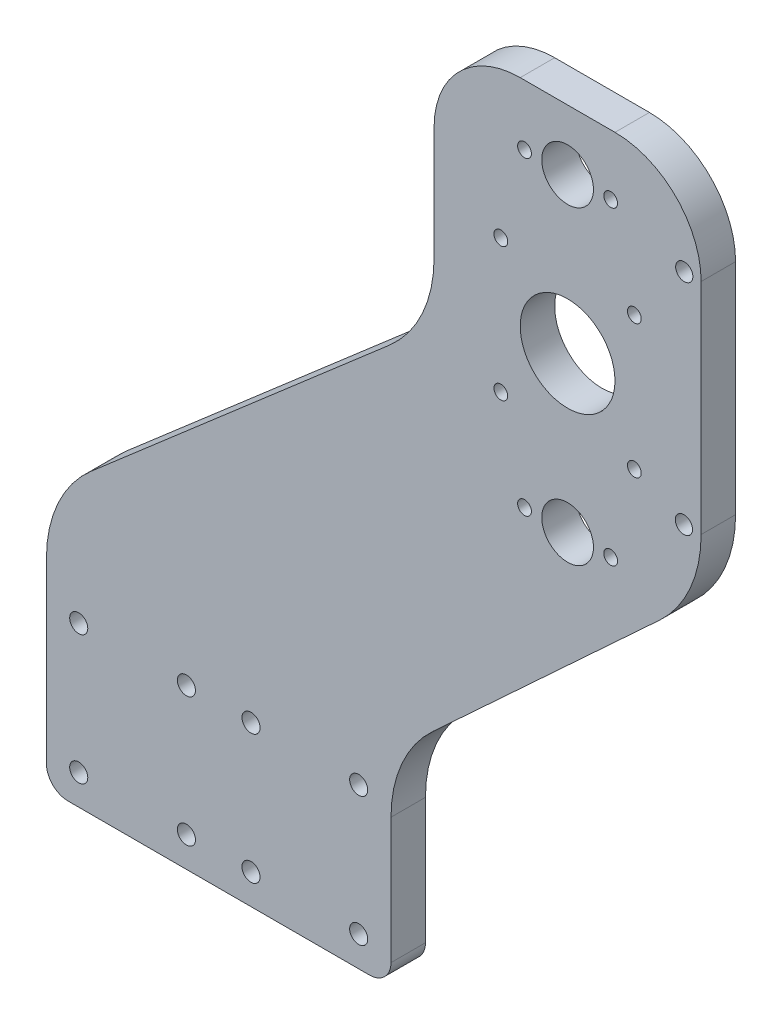
SolidWorks part; units mm, degrees
ref_plane "Front Plane" through (0, 0, 0) normal (0, 0, 1) x (1, 0, 0)
ref_plane "Top Plane" through (0, 0, 0) normal (0, 1, 0) x (1, 0, 0)
ref_plane "Right Plane" through (0, 0, 0) normal (1, 0, 0) x (0, 0, -1)
sketch "Sketch1" plane through (0, 0, 0) normal (0, 0, 1) x (1, 0, 0)
  line L0 (-23.731, -89.4451) -> (-23.731, -15.4242) construction
  line L1 (-58.731, -89.4451) -> (11.269, -89.4451)
  line L2 (-63.731, -84.4451) -> (-63.731, -43.1503)
  line L3 (-63.731, -84.4451) -> (-23.731, -84.4451) construction
  line L4 (16.269, -84.4451) -> (16.269, -55.2061)
  line L5 (46.269, 108.4996) -> (68.269, 108.4996)
  line L6 (26.269, 88.4996) -> (26.269, 62.2048)
  line L7 (57.269, 108.4996) -> (57.269, 22.5596) construction
  line L8 (88.269, 88.4996) -> (88.269, 37.6266)
  line L9 (-43.731, -67.4451) -> (-43.731, -84.4451) construction
  line L10 (-56.231, -52.4451) -> (-31.231, -52.4451) construction
  line L11 (15.9089, 39.5272) -> (-53.371, -20.4728)
  line L12 (78.6402, 15.6036) -> (25.8977, -33.1831)
  line L13 (-56.231, -52.4451) -> (-56.231, -82.4451) construction
  line L14 (-56.231, -82.4451) -> (-31.231, -82.4451) construction
  line L15 (-31.231, -52.4451) -> (-31.231, -82.4451) construction
  line L16 (-56.231, -52.4451) -> (-31.231, -82.4451) construction
  line L17 (-56.231, -82.4451) -> (-31.231, -52.4451) construction
  line L18 (57.269, 94.4996) -> (57.269, 22.5596) construction
  line L20 (41.769, 43.0296) -> (72.769, 43.0296) construction
  line L21 (41.769, 43.0296) -> (41.769, 74.0296) construction
  line L22 (41.769, 74.0296) -> (72.769, 74.0296) construction
  line L23 (72.769, 43.0296) -> (72.769, 74.0296) construction
  line L24 (41.769, 43.0296) -> (72.769, 74.0296) construction
  line L25 (41.769, 74.0296) -> (72.769, 43.0296) construction
  arc A0 (78.6402, 15.6036) -> (88.269, 37.6266) centre (58.269, 37.6266) ccw
  arc A1 (15.9089, 39.5272) -> (26.269, 62.2048) centre (-3.731, 62.2048) ccw
  arc A2 (16.269, -55.2061) -> (25.8977, -33.1831) centre (46.269, -55.2061) cw
  arc A3 (-63.731, -43.1503) -> (-53.371, -20.4728) centre (-33.731, -43.1503) cw
  arc A4 (88.269, 88.4996) -> (68.269, 108.4996) centre (68.269, 88.4996) ccw
  arc A5 (46.269, 108.4996) -> (26.269, 88.4996) centre (46.269, 88.4996) ccw
  arc A6 (16.269, -84.4451) -> (11.269, -89.4451) centre (11.269, -84.4451) cw
  arc A7 (-58.731, -89.4451) -> (-63.731, -84.4451) centre (-58.731, -84.4451) cw
  circle A8 centre (-56.231, -52.4451) radius 2.1
  circle A9 centre (-31.231, -52.4451) radius 2.1
  circle A10 centre (-31.231, -82.4451) radius 2.1
  circle A11 centre (-56.231, -82.4451) radius 2.1
  circle A12 centre (8.769, -82.4451) radius 2.1
  circle A13 centre (-16.231, -82.4451) radius 2.1
  circle A14 centre (-16.231, -52.4451) radius 2.1
  circle A15 centre (8.769, -52.4451) radius 2.1
  circle A16 centre (57.269, 94.4996) radius 6
  circle A17 centre (57.269, 22.5596) radius 6
  circle A18 centre (57.269, 58.5296) radius 11
  circle A19 centre (41.769, 74.0296) radius 1.6
  circle A20 centre (72.769, 74.0296) radius 1.6
  circle A21 centre (72.769, 43.0296) radius 1.6
  circle A22 centre (41.769, 43.0296) radius 1.6
  circle A23 centre (84.269, 37.6266) radius 2
  circle A24 centre (84.3518, 88.5185) radius 2
  circle A25 centre (47.269, 94.4996) radius 1.6
  circle A26 centre (47.269, 22.5596) radius 1.6
  circle A27 centre (67.269, 94.4996) radius 1.6
  circle A28 centre (67.269, 22.5596) radius 1.6
  point P0 (0, 0)
  point P1 (57.269, 82.2289)
  point P15 (26.269, 48.4996)
  point P20 (-63.731, -29.4451)
  point P23 (88.269, 108.4996)
  point P26 (26.269, 108.4996)
  point P29 (16.269, -89.4451)
  point P32 (-63.731, -89.4451)
  point P35 (-43.731, -67.4451)
  dimension "D5" = 30
  dimension "D6" = 20
  dimension "D7" = 5
  dimension "D14" = 71.94
  dimension "D12" = 31
  dimension "D17" = 4
  dimension "D18" = 10
  dimension "D19" = 10
  dimension "D1" = 80
  dimension "D2" = 22
  dimension "D3" = 90
  dimension "D4" = 60
  dimension "D8" = 25
  dimension "D9" = 60
  dimension "D10" = 22
  dimension "D11" = 60
  dimension "D13" = 30
  dimension "D15" = 14
  dimension "D16" = 31
extrude "Boss-Extrude1" add sketch "Sketch1" along normal blind 8
